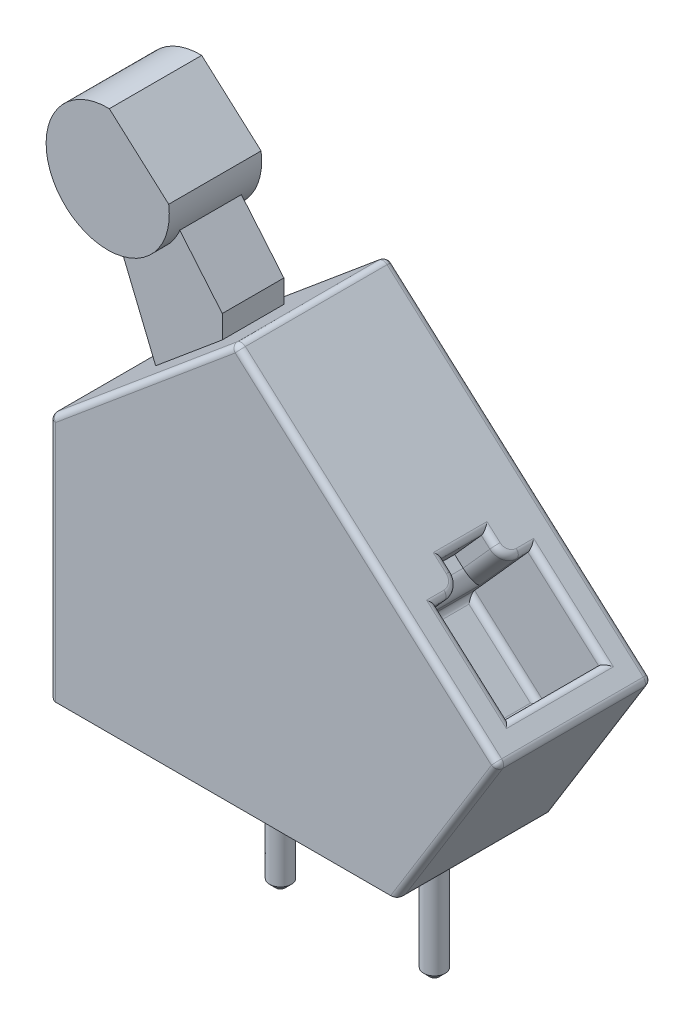
SolidWorks part; units mm, degrees
ref_plane "Front" through (0, 0, 0) normal (0, 0, 1) x (1, 0, 0)
ref_plane "Top" through (0, 0, 0) normal (0, 1, 0) x (1, 0, 0)
ref_plane "Right" through (0, 0, 0) normal (1, 0, 0) x (0, 0, -1)
sketch "Sketch1" plane through (0, 0, 0) normal (0, 0, 1) x (1, 0, 0)
  line L0 (0, 0) -> (0, 7.9588)
  line L1 (0, 7.9588) -> (6.0336, 13)
  line L2 (6.0336, 13) -> (14.6076, 5.3389)
  line L3 (14.6076, 5.3389) -> (11.312, 0)
  line L4 (11.312, 0) -> (0, 0)
  dimension "D1" = 13
extrude "Boss-Extrude1" add sketch "Sketch1" along normal blind 5
sketch "Sketch2" plane through (9.1376, 10.2265, 0) normal (0.6663, 0.7457, 0) x (0.7457, -0.6663, 0)
  line L0 (7.3355, -2.5) -> (-4.1626, -2.5) construction
  line L1 (7.3355, -5) -> (7.3355, 0) construction
  line L2 (-4.1626, -5) -> (-4.1626, 0) construction
  line L4 (3.3452, -4.0382) -> (6.4216, -4.0382)
  line L5 (3.3452, -4.0382) -> (3.3452, -0.9618)
  line L6 (3.3452, -0.9618) -> (6.4216, -0.9618)
  line L7 (6.4216, -4.0382) -> (6.4216, -0.9618)
  line L8 (3.3452, -4.0382) -> (6.4216, -0.9618) construction
  line L9 (3.3452, -0.9618) -> (6.4216, -4.0382) construction
  point P6 (4.8834, -2.5)
extrude "Cut-Extrude1" cut sketch "Sketch2" against normal blind 3
sketch "Sketch3" plane through (9.1376, 10.2265, 0) normal (0.6663, 0.7457, 0) x (0.7457, -0.6663, 0)
  line L0 (3.3452, -0.9618) -> (3.3452, -4.0382) construction
  line L1 (4.2162, -3.1734) -> (2.4743, -3.1734)
  line L2 (4.2162, -3.1734) -> (4.2162, -1.8266)
  line L3 (4.2162, -1.8266) -> (2.4743, -1.8266)
  line L4 (2.4743, -3.1734) -> (2.4743, -1.8266)
  line L5 (4.2162, -3.1734) -> (2.4743, -1.8266) construction
  line L6 (4.2162, -1.8266) -> (2.4743, -3.1734) construction
  point P0 (3.3452, -2.5)
extrude "Cut-Extrude2" cut sketch "Sketch3" against normal blind 1.5
ref_plane "Plane1" through (0, 0, 2.5) normal (0, 0, 1) x (1, 0, 0)
sketch "Sketch5" plane through (0, 0, 2.5) normal (0, 0, 1) x (1, 0, 0)
  line L0 (1.9469, 9.5854) -> (0.1037, 14.0756)
  line L1 (6.0336, 13) -> (0, 7.9588) construction
  line L2 (0.1037, 14.0756) -> (1.6749, 15.0508)
  line L3 (1.6749, 15.0508) -> (4.11, 12.1364)
  line L4 (4.11, 12.1364) -> (4.11, 11.3928)
  line L5 (1.9469, 9.5854) -> (4.11, 11.3928)
extrude "Boss-Extrude2" add sketch "Sketch5" along normal mid plane 2 separate body
sketch "Sketch7" plane through (0, 0, 2.5) normal (0, 0, 1) x (1, 0, 0)
  line L0 (1.6749, 15.0508) -> (0.1037, 14.0756) construction
  line L1 (0.9419, 16.5625) -> (2.8701, 14.8395)
  line L2 (14.6076, 5.3389) -> (6.0336, 13) construction
  circle A0 centre (0.8893, 14.5632) radius 2 construction
  arc A1 (2.8701, 14.8395) -> (0.9419, 16.5625) centre (0.8893, 14.5632) cw
  dimension "D1" = 2
extrude "Boss-Extrude3" add sketch "Sketch7" along normal mid plane 3 separate body
sketch "Sketch8" plane through (0, 0, 0) normal (0, -1, 0) x (-1, 0, 0)
  line L0 (-7.15, -2.5) -> (7.15, -2.5) construction
  line L1 (0, -5) -> (0, 0) construction
  circle A0 centre (-5, -2.5) radius 0.35
  circle A1 centre (-10, -2.5) radius 0.35
  dimension "D1" = 5
  dimension "D2" = 0.7
  dimension "D3" = 5
extrude "Boss-Extrude4" add sketch "Sketch8" along normal blind 4 separate body
chamfer "Chamfer1" distance 0.2 angle 45 1 edges at (5, -4, 2.15)
chamfer "Chamfer2" distance 0.2 angle 45 1 edges at (10, -4, 2.15)
fillet "Fillet1" radius 0.2 4 edges at (10.7803, 4.7357, 4.0382) (9.6332, 5.7606, 2.5) (10.7803, 4.7357, 0.9618) (11.9273, 3.7108, 2.5)
fillet "Fillet2" radius 0.2 21 edges at (11.312, 0, 2.5) (12.9598, 2.6695, 5) (12.9598, 2.6695, 0) (0, 3.9794, 5) (0, 0, 2.5) (0, 3.9794, 0) (3.0168, 10.4794, 5) (0, 7.9588, 2.5) (3.0168, 10.4794, 0) (14.6076, 5.3389, 2.5) (10.3206, 9.1695, 5) (6.0336, 13, 2.5) (10.3206, 9.1695, 0) (11.3074, 8.2878, 3.1734) (11.6321, 7.9976, 3.6058) (12.7791, 6.9727, 4.0382) (13.9262, 5.9478, 2.5) (12.7791, 6.9727, 0.9618) (11.6321, 7.9976, 1.3942) (11.3074, 8.2878, 1.8266) (10.9826, 8.5779, 2.5)
fillet "Fillet3" radius 0.5 1 edges at (10.6327, 6.8791, 2.5)
fillet "Fillet4" radius 0.5 4 edges at (11.5494, 7.993, 3.232) (11.5494, 7.993, 1.768) (10.8992, 7.1774, 1.8266) (10.8992, 7.1774, 3.1734)
